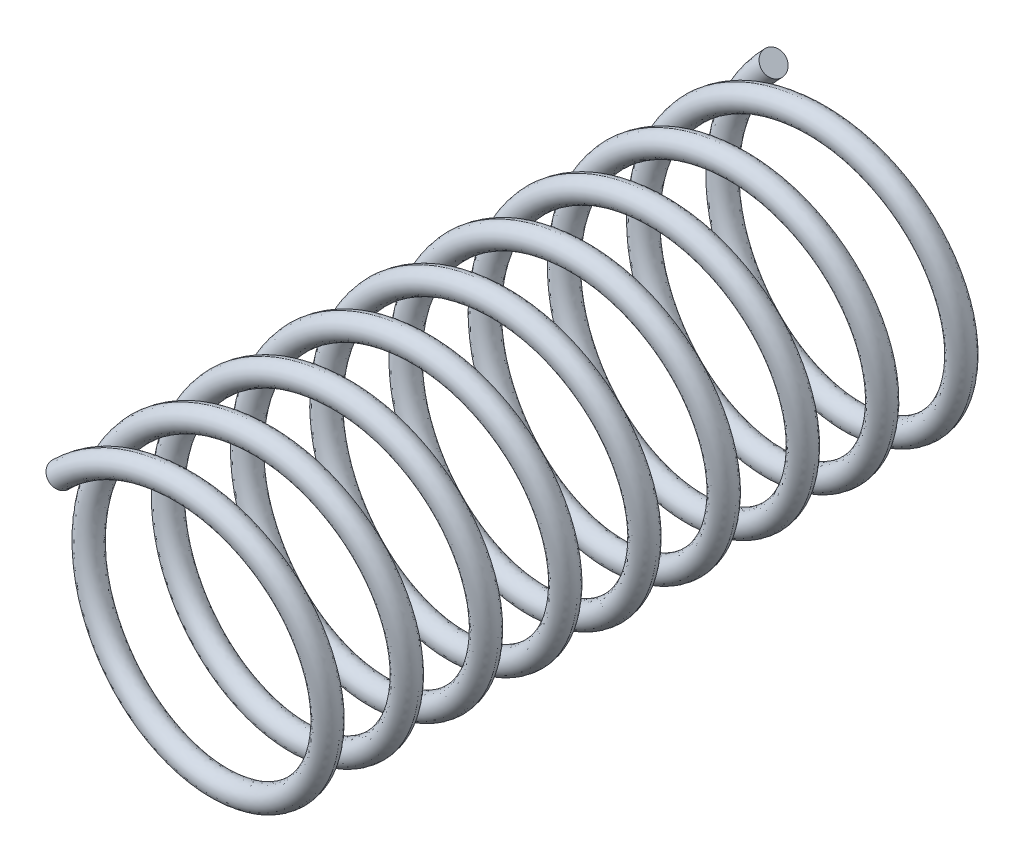
SolidWorks part; units mm, degrees
ref_plane "前视基准面" through (0, 0, 0) normal (0, 0, 1) x (1, 0, 0)
ref_plane "上视基准面" through (0, 0, 0) normal (0, 1, 0) x (1, 0, 0)
ref_plane "右视基准面" through (0, 0, 0) normal (1, 0, 0) x (0, 0, -1)
sketch "草图1" plane through (0, 0, 0) normal (0, 0, 1) x (1, 0, 0)
  circle A0 centre (0, 0) radius 3.5
  dimension "D1" = 7
curve "螺旋线/涡状线1" pitch 2 height 18 turns 9
sketch "草图2" plane through (0, 0, 0) normal (0, 1, 0) x (1, 0, 0)
  circle A0 centre (3.5, 0.75) radius 0.3
  dimension "D1" = 0.6
sweep "扫描1" add profiles "草图2" path "螺旋线/涡状线1"
